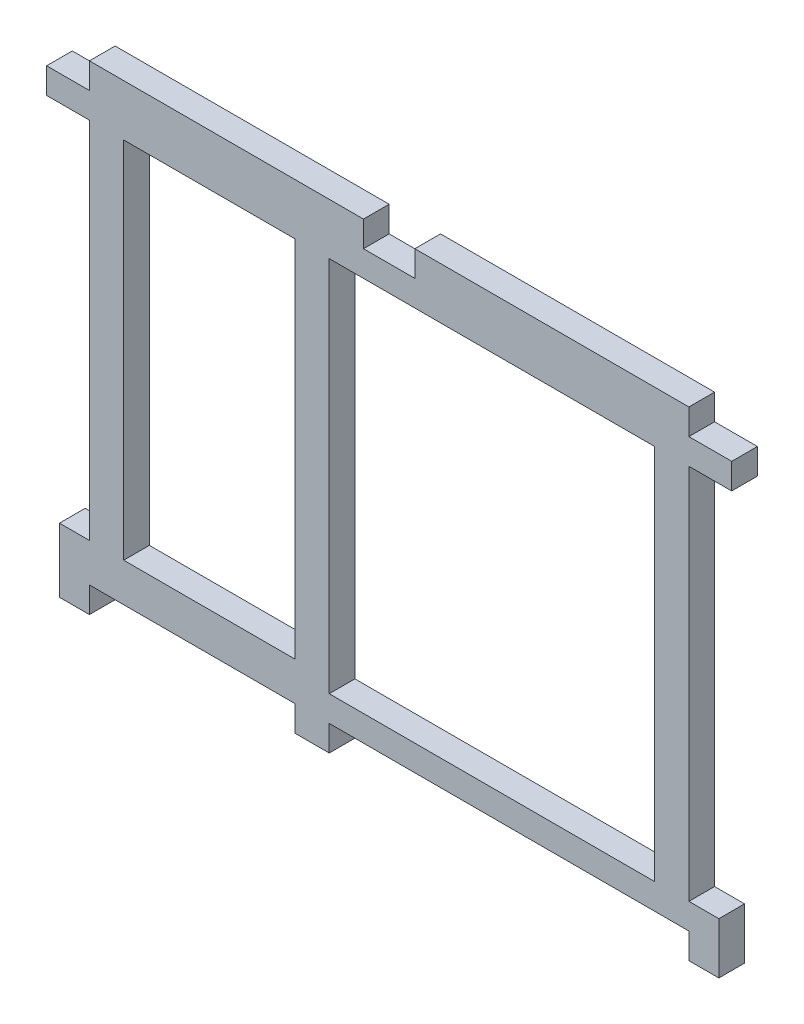
SolidWorks part; units mm, degrees
material "Custom Plastic"
ref_plane "Front Plane" through (0, 0, 0) normal (0, 0, 1) x (1, 0, 0)
ref_plane "Top Plane" through (0, 0, 0) normal (0, 1, 0) x (1, 0, 0)
ref_plane "Right Plane" through (0, 0, 0) normal (1, 0, 0) x (0, 0, -1)
sketch "Sketch1" plane through (0, 0, 0) normal (0, 0, 1) x (1, 0, 0)
  line L75 (5, -3) -> (0, -3)
  line L76 (0, -3) -> (0, 0)
  line L77 (0, 0) -> (5, 0)
  line L78 (5, 0) -> (5, 3)
  line L79 (5, 3) -> (37, 3)
  line L80 (37, 3) -> (37, 0)
  line L81 (37, 0) -> (43, 0)
  line L82 (43, 0) -> (43, 3)
  line L83 (43, 3) -> (75, 3)
  line L84 (75, 3) -> (75, 0)
  line L85 (75, 0) -> (80, 0)
  line L86 (80, 0) -> (80, -3)
  line L87 (80, -3) -> (75, -3)
  line L88 (75, -3) -> (75, -47)
  line L89 (75, -47) -> (78.5, -47)
  line L90 (78.5, -47) -> (78.5, -53)
  line L91 (78.5, -53) -> (75, -53)
  line L92 (75, -53) -> (75, -50)
  line L93 (75, -50) -> (33, -50)
  line L94 (33, -50) -> (33, -53)
  line L95 (33, -53) -> (29, -53)
  line L96 (29, -53) -> (29, -50)
  line L97 (29, -50) -> (5, -50)
  line L98 (5, -50) -> (5, -53)
  line L99 (5, -53) -> (1.5, -53)
  line L100 (1.5, -53) -> (1.5, -45.5)
  line L101 (1.5, -45.5) -> (5, -45.5)
  line L102 (5, -3) -> (5, -45.5)
  line L103 (9, -45.5) -> (29, -45.5)
  line L104 (29, -45.5) -> (29, -3)
  line L105 (29, -3) -> (9, -3)
  line L106 (9, -3) -> (9, -45.5)
  line L107 (33, -3) -> (33, -47)
  line L108 (33, -47) -> (71, -47)
  line L109 (71, -47) -> (71, -3)
  line L110 (71, -3) -> (33, -3)
  point P56 (76.75, -47)
  dimension "D4" = 44
  dimension "D13" = 6
  dimension "D14" = 3
  dimension "D15" = 3
  dimension "D16" = 32
  dimension "D17" = 32
  dimension "D18" = 5
  dimension "D19" = 5
  dimension "D20" = 44
  dimension "D21" = 6
  dimension "D22" = 3.5
  dimension "D23" = 3
  dimension "D24" = 42
  dimension "D25" = 4
  dimension "D26" = 24
  dimension "D27" = 3.5
  dimension "D28" = 7.5
  dimension "D29" = 4
  dimension "D30" = 4
  dimension "D31" = 20
extrude "Boss-Extrude1" add sketch "Sketch1" along normal blind 3
